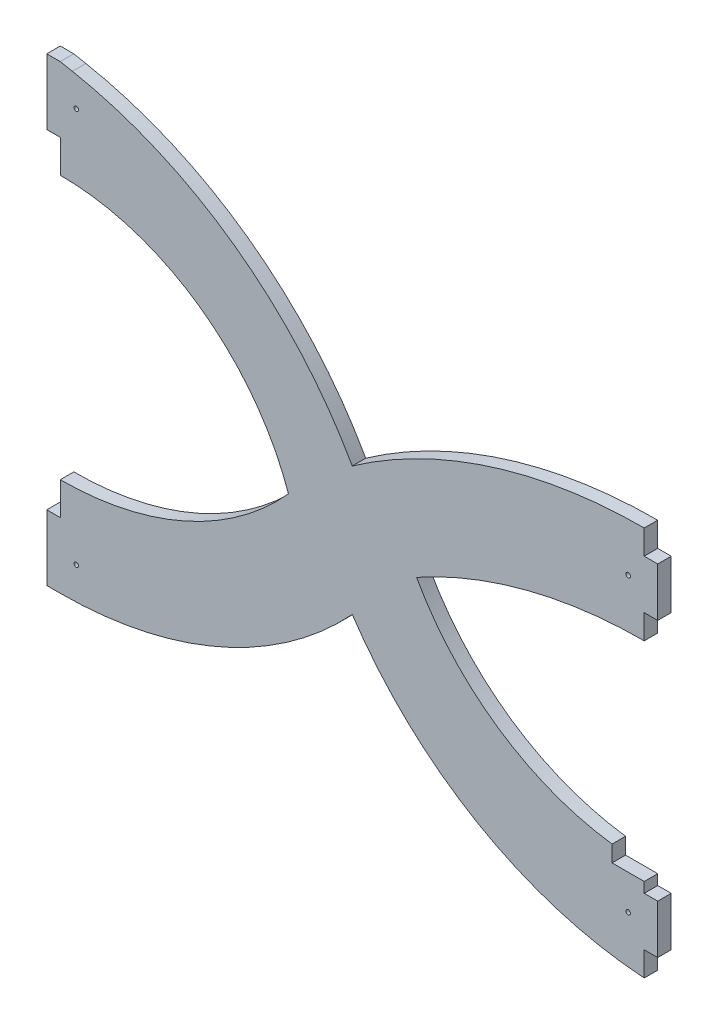
SolidWorks part; units mm, degrees
ref_plane "Front Plane" through (0, 0, 0) normal (0, 0, 1) x (1, 0, 0)
ref_plane "Top Plane" through (0, 0, 0) normal (0, 1, 0) x (1, 0, 0)
ref_plane "Right Plane" through (0, 0, 0) normal (1, 0, 0) x (0, 0, -1)
sketch "Sketch1" plane through (0, 0, 0) normal (0, 0, 1) x (1, 0, 0)
  line L1 (-141.9798, 90.4351) -> (99.3202, 90.4351)
  line L2 (-141.9798, 90.4351) -> (-141.9798, -107.6849)
  line L3 (-141.9798, -107.6849) -> (99.3202, -107.6849)
  line L4 (99.3202, 90.4351) -> (99.3202, -107.6849)
  dimension "D1" = 241.3
  dimension "D2" = 198.12
extrude "Boss-Extrude1" add sketch "Sketch1" along normal blind 5.334
sketch "Sketch2" plane through (0, 0, 5.334) normal (0, 0, 1) x (1, 0, 0)
  line L0 (99.3202, -107.6849) -> (99.3202, 90.4351) construction
  line L1 (99.3202, -107.6849) -> (93.9862, -107.6849)
  line L2 (99.3202, -107.6849) -> (99.3202, -98.0329)
  line L3 (99.3202, -98.0329) -> (93.9862, -98.0329)
  line L4 (93.9862, -107.6849) -> (93.9862, -98.0329)
  line L5 (99.3202, -78.7289) -> (93.9862, -78.7289)
  line L7 (93.9862, 17.2831) -> (99.3202, 17.2831)
  line L8 (93.9862, 17.2831) -> (93.9862, -78.7289)
  line L9 (93.9862, 36.5871) -> (93.9862, 17.2831) construction
  line L10 (99.3202, 90.4351) -> (93.9862, 90.4351)
  line L11 (99.3202, 90.4351) -> (99.3202, 36.5871)
  line L12 (99.3202, 36.5871) -> (93.9862, 36.5871)
  line L13 (93.9862, 90.4351) -> (93.9862, 36.5871)
  line L16 (99.3202, 17.2831) -> (99.3202, -78.7289)
  line L18 (93.9862, -78.7289) -> (93.9862, -98.0329) construction
  dimension "D1" = 5.334
  dimension "D3" = 19.304
  dimension "D4" = 9.652
  dimension "D5" = 19.304
  dimension "D2" = 96.012
extrude "Cut-Extrude1" cut sketch "Sketch2" against normal through all
sketch "Sketch3" plane through (0, 0, 5.334) normal (0, 0, 1) x (1, 0, 0)
  line L1 (-141.9798, -107.6849) -> (-136.6458, -107.6849)
  line L2 (-141.9798, -107.6849) -> (-141.9798, -91.4289)
  line L3 (-141.9798, -91.4289) -> (-136.6458, -91.4289)
  line L4 (-136.6458, -107.6849) -> (-136.6458, -91.4289)
  line L5 (-141.9798, 90.4351) -> (-141.9798, -107.6849) construction
  line L6 (-136.6458, -65.5209) -> (-141.9798, -65.5209)
  line L7 (-136.6458, -65.5209) -> (-136.6458, 64.5271)
  line L8 (-136.6458, 64.5271) -> (-141.9798, 64.5271)
  line L9 (-141.9798, -65.5209) -> (-141.9798, 64.5271)
  line L10 (-136.6458, -65.5209) -> (-136.6458, -91.4289) construction
  line L11 (-136.6458, 64.5271) -> (-136.6458, 90.4351) construction
  line L12 (93.9862, 90.4351) -> (-141.9798, 90.4351) construction
  dimension "D1" = 16.256
  dimension "D2" = 25.908
  dimension "D3" = 25.908
  dimension "D4" = 5.334
extrude "Cut-Extrude2" cut sketch "Sketch3" against normal through all
sketch "Sketch5" plane through (0, 0, 5.334) normal (0, 0, 1) x (1, 0, 0)
  line L0 (-136.6458, -91.4289) -> (93.9862, -107.6849) construction
  line L1 (-136.6458, -91.4289) -> (93.9862, -107.6849)
  line L2 (-136.6458, -91.4289) -> (-136.6458, -146.6044)
  line L3 (93.9862, -107.6849) -> (93.9862, -162.8604)
  line L4 (-136.6458, -146.6044) -> (93.9862, -162.8604)
extrude "Cut-Extrude5" cut sketch "Sketch5" against normal through all
sketch "Sketch6" plane through (0, 0, 5.334) normal (0, 0, 1) x (1, 0, 0)
  line L0 (-136.6458, 64.5271) -> (-136.6458, 90.4351) construction
  line L1 (93.9862, 90.4351) -> (-141.9798, 90.4351) construction
  line L2 (93.9862, 36.5871) -> (93.9862, 46.2391) construction
  line L3 (93.9862, 90.4351) -> (93.9862, 36.5871) construction
  line L4 (-136.6458, 90.4351) -> (93.9862, 46.2391)
  line L5 (-136.6458, 90.4351) -> (-136.6458, 134.6311)
  line L6 (93.9862, 46.2391) -> (93.9862, 90.4351)
  line L7 (-136.6458, 134.6311) -> (93.9862, 90.4351)
  dimension "D1" = 9.652
extrude "Cut-Extrude6" cut sketch "Sketch6" against normal through all
sketch "Sketch7" plane through (0, 0, 5.334) normal (0, 0, 1) x (1, 0, 0)
  line L0 (-21.3298, 68.3371) -> (-21.3298, -99.5569) construction
  line L1 (-136.6458, 90.4351) -> (93.9862, 46.2391) construction
  line L2 (93.9862, -107.6849) -> (-136.6458, -91.4289) construction
  line L3 (93.9862, -30.7229) -> (-136.6458, -0.4969) construction
  line L4 (93.9862, 17.2831) -> (93.9862, -78.7289) construction
  line L5 (-136.6458, -65.5209) -> (-136.6458, 64.5271) construction
  line L6 (-136.6458, 64.5271) -> (-136.6458, 51.5731) construction
  line L7 (-136.6458, -65.5209) -> (-136.6458, -52.5669) construction
  line L8 (93.9862, 17.2831) -> (93.9862, 7.6311) construction
  line L9 (93.9862, -78.7289) -> (93.9862, -69.0769) construction
  line L10 (-136.6458, 64.5271) -> (-131.8569, 89.5174) construction
  line L11 (93.9862, 36.5871) -> (93.9862, 46.2391) construction
  line L12 (-131.8569, 89.5174) -> (93.9862, 46.2391)
  line L13 (-136.6458, -65.5209) -> (-136.6458, -91.4289) construction
  line L14 (93.9862, -98.0329) -> (93.3092, -107.6372) construction
  line L15 (-136.6458, -91.4289) -> (93.3092, -107.6372)
  circle A0 centre (-21.3298, -15.6099) radius 25.4 construction
  arc A1 (93.9862, 7.6311) -> (4.0702, -15.6099) centre (93.9862, -177.9253) ccw
  arc A2 (4.0702, -15.6099) -> (92.3478, -69.0769) centre (94.8631, 34.6856) ccw
  arc A3 (92.3478, -69.0769) -> (93.9862, 7.6311) centre (93.2775, -30.7253) ccw
  arc A4 (-136.6458, 51.5731) -> (-46.5144, -12.3093) centre (-136.6458, -43.9511) cw
  arc A5 (-136.6458, -52.5669) -> (-46.5144, -12.3093) centre (-136.6458, 68.4578) ccw
  arc A6 (-136.6458, 51.5731) -> (-136.6458, -52.5669) centre (-136.6458, -0.4969) ccw
  arc A7 (-131.8569, 89.5174) -> (-21.3298, 9.7901) centre (-162.2521, -69.0963) cw
  arc A8 (93.9862, 46.2391) -> (-21.3298, 9.7901) centre (93.9862, -154.4017) ccw
  arc A9 (-136.6458, -91.4289) -> (-21.3298, -41.0099) centre (-136.6458, 65.6533) ccw
  arc A10 (93.3092, -107.6372) -> (-21.3298, -41.0099) centre (103.8923, 42.5098) cw
extrude "Cut-Extrude7" cut sketch "Sketch7" against normal through all
sketch "Sketch8" plane through (0, 0, 5.334) normal (0, 0, 1) x (1, 0, 0)
  line L0 (-141.9798, 90.4351) -> (-141.9798, 64.5271) construction
  line L1 (-141.9798, 77.4811) -> (-82.7249, 77.4811) construction
  line L2 (-141.9798, 77.4811) -> (-141.9798, -78.4749) construction
  line L3 (-141.9798, -65.5209) -> (-141.9798, -91.4289) construction
  line L4 (-141.9798, -0.4969) -> (-61.4833, -0.4969) construction
  circle A0 centre (-130.2958, 77.4811) radius 0.889
  circle A1 centre (-130.2958, -78.4749) radius 0.889
  point P2 (-141.9798, 77.4811)
  dimension "D3" = 1.778
  dimension "D1" = 11.684
  dimension "D2" = 0
extrude "Cut-Extrude8" cut sketch "Sketch8" against normal through all
sketch "Sketch9" plane through (0, 0, 5.334) normal (0, 0, 1) x (1, 0, 0)
  line L0 (99.3202, 26.9351) -> (60.8503, 26.9351) construction
  line L1 (99.3202, 17.2831) -> (99.3202, 36.5871) construction
  line L2 (99.3202, -88.3809) -> (53.0576, -88.3809) construction
  line L3 (99.3202, -98.0329) -> (99.3202, -78.7289) construction
  line L4 (99.3202, 26.9351) -> (99.3202, -88.3809) construction
  line L5 (99.3202, -30.7229) -> (41.8715, -30.7229) construction
  line L6 (93.9862, 46.2391) -> (93.9862, 36.5871) construction
  circle A0 centre (87.6362, 26.9351) radius 0.889
  circle A1 centre (87.6362, -88.3809) radius 0.889
  dimension "D1" = 1.778
  dimension "D2" = 0
  dimension "D3" = 6.35
extrude "Cut-Extrude9" cut sketch "Sketch9" against normal through all
sketch "Sketch10" plane through (0, 0, 5.334) normal (0, 0, 1) x (1, 0, 0)
  line L0 (93.9862, -69.0816) -> (93.9862, -78.7289) construction
  line L1 (93.9862, -74.6649) -> (81.2862, -74.6649)
  line L2 (93.9862, -74.6649) -> (93.9862, -53.5121)
  line L3 (93.9862, -53.5121) -> (81.2862, -53.5121)
  line L4 (81.2862, -74.6649) -> (81.2862, -53.5121)
  line L5 (93.9862, -78.7289) -> (99.3202, -78.7289) construction
  dimension "D1" = 4.064
  dimension "D2" = 12.7
extrude "Cut-Extrude10" cut sketch "Sketch10" against normal through all
equation "\"MDF\"= .21in"
equation "\"Foamcore\"= .13in"
equation "\"Gmaterial\"= \"MDF\""
equation "\"D1@Boss-Extrude1\"=\"MDF\""
equation "\"D1@Sketch2\"=\"MDF\""
equation "\"D4@Sketch3\"=\"MDF\""
equation "\"D1@Sketch8\"=0.25+\"MDF\""
